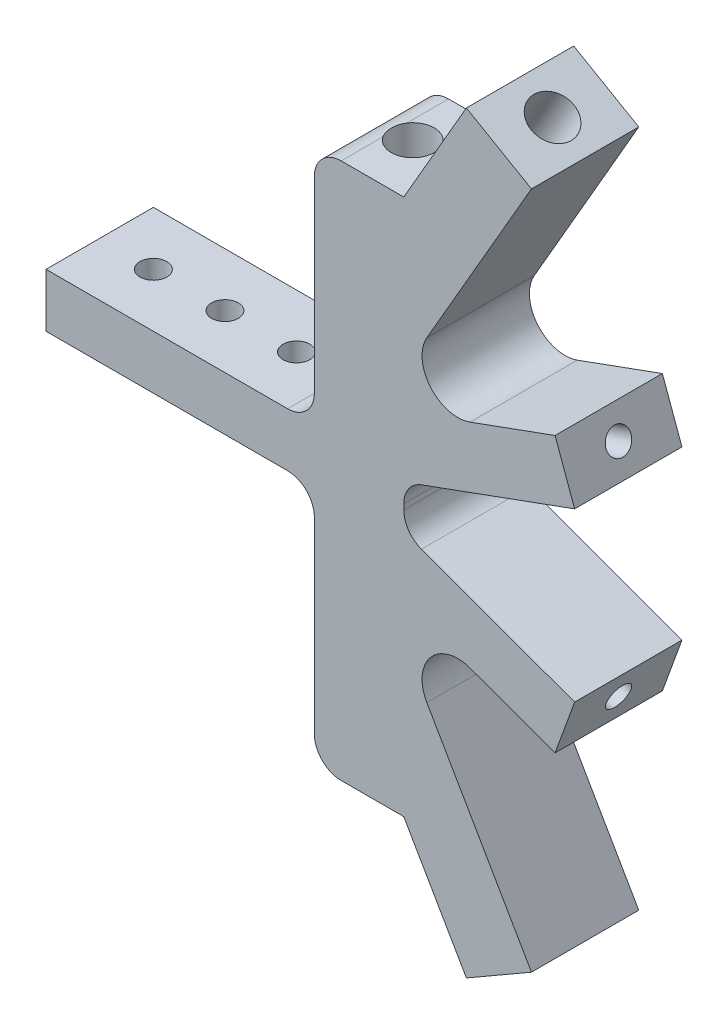
SolidWorks part; units mm, degrees
ref_plane "前基準面" through (0, 0, 0) normal (0, 0, 1) x (1, 0, 0)
ref_plane "上基準面" through (0, 0, 0) normal (0, 1, 0) x (1, 0, 0)
ref_plane "右基準面" through (0, 0, 0) normal (1, 0, 0) x (0, 0, -1)
sketch "草圖1" plane through (0, 0, 0) normal (0, 0, 1) x (1, 0, 0)
  line L0 (0, 23.7611) -> (0, -45.4717) construction
  line L1 (-15.5994, 0) -> (20.5033, 0) construction
  line L2 (-2.5, 15) -> (2.5, 15)
  line L3 (-2.5, 15) -> (-2.5, 1.5)
  line L4 (-2.5, -15) -> (2.5, -15)
  line L5 (2.5, 6.6) -> (2.5, 4.6054)
  line L6 (-2.5, 15) -> (2.5, -15) construction
  line L7 (-2.5, -15) -> (2.5, 15) construction
  line L8 (2.5, 15) -> (6, 21.0622)
  line L9 (6, 21.0622) -> (9.6373, 18.9622)
  line L10 (9.6373, 18.9622) -> (2.5, 6.6)
  line L11 (2.5, -15) -> (6, -21.0622)
  line L12 (6, -21.0622) -> (9.6373, -18.9622)
  line L13 (9.6373, -18.9622) -> (2.5, -6.6)
  line L14 (2.5, 4.6054) -> (10.9572, 7.6836)
  line L15 (10.9572, 7.6836) -> (12.0517, 4.6765)
  line L16 (12.0517, 4.6765) -> (2.5, 1.2)
  line L17 (2.5, -1.2) -> (12.0517, -4.6765)
  line L18 (12.0517, -4.6765) -> (10.9572, -7.6836)
  line L19 (10.9572, -7.6836) -> (2.5, -4.6054)
  line L20 (2.5, 1.2) -> (2.5, -1.2)
  line L21 (-17.5, 1.5) -> (-2.5, 1.5)
  line L22 (-17.5, 1.5) -> (-17.5, -1.5)
  line L23 (-17.5, -1.5) -> (-2.5, -1.5)
  line L25 (-17.5, 1.5) -> (-2.5, -1.5) construction
  line L26 (-17.5, -1.5) -> (-2.5, 1.5) construction
  line L27 (2.5, -4.6054) -> (2.5, -6.6)
  line L28 (-2.5, -1.5) -> (-2.5, -15)
  point P3 (0, 0)
  point P22 (-10, 0)
  dimension "D1" = 5
  dimension "D2" = 30
  dimension "D3" = 60
  dimension "D4" = 60
  dimension "D5" = 7
  dimension "D6" = 7
  dimension "D7" = 40
  dimension "D8" = 40
  dimension "D9" = 9
  dimension "D10" = 9
  dimension "D11" = 4.2
  dimension "D12" = 3.2
  dimension "D13" = 1.2
  dimension "D14" = 1.2
  dimension "D15" = 1.5
  dimension "D16" = 3
  dimension "D17" = 15
  dimension "D18" = 4.2
extrude "填料-伸長1" add sketch "草圖1" along normal blind 6
fillet "圓角4" radius 1.5 6 edges at (-2.5, -1.5, 3) (-2.5, 1.5, 3) (2.5, -4.6054, 3) (2.5, -1.2, 3) (2.5, 1.2, 3) (2.5, 4.6054, 3)
fillet "圓角5" radius 2 2 edges at (2.5, -6.6, 3) (2.5, 6.6, 3)
sketch "草圖7" plane through (10.6202, 18.3947, 0) normal (0.5, 0.866, 0) x (0.866, -0.5, 0)
  line L0 (-1.1349, -6) -> (-1.1349, 0) construction
  line L1 (-1.1349, 0) -> (-5.3349, 0) construction
  circle A0 centre (-3.2349, -3) radius 1.2
  dimension "D1" = 2.4
  dimension "D2" = 2.1
  dimension "D3" = 3
extrude "除料-伸長6" cut sketch "草圖7" against normal blind 10
sketch "草圖8" plane through (10.6202, -18.3947, 0) normal (0.5, -0.866, 0) x (0.866, 0.5, 0)
  line L2 (-1.1349, 6) -> (-1.1349, 0) construction
  line L3 (-5.3349, 0) -> (-1.1349, 0) construction
  circle A0 centre (-3.2349, 3) radius 0.7
  dimension "D3" = 1.4
  dimension "D1" = 3
  dimension "D2" = 2.1
extrude "除料-伸長7" cut sketch "草圖8" against normal blind 10
sketch "草圖9" plane through (12.1449, -4.4204, 0) normal (0.9397, -0.342, 0) x (0, 0, -1)
  line L1 (0, -3.4726) -> (0, -0.2726) construction
  line L2 (-6, -3.4726) -> (0, -3.4726) construction
  circle A0 centre (-3, -1.8726) radius 0.7
  dimension "D3" = 1.4
  dimension "D1" = 1.6
  dimension "D2" = 3
extrude "除料-伸長8" cut sketch "草圖9" against normal blind 10
sketch "草圖10" plane through (12.1449, 4.4204, 0) normal (0.9397, 0.342, 0) x (0, 0, -1)
  line L0 (-6, 3.4726) -> (0, 3.4726) construction
  line L1 (0, 0.2726) -> (0, 3.4726) construction
  circle A0 centre (-3, 1.8726) radius 0.7
  dimension "D3" = 1.4
  dimension "D1" = 1.6
  dimension "D2" = 3
extrude "除料-伸長9" cut sketch "草圖10" against normal blind 10
sketch "草圖11" plane through (0, -15, 0) normal (0, -1, 0) x (1, 0, 0)
  line L0 (2.5, 6) -> (-2.5, 6) construction
  circle A0 centre (0, 3) radius 1.2
  point P2 (0, 6)
  dimension "D1" = 2.4
  dimension "D2" = 3
extrude "除料-伸長10" cut sketch "草圖11" against normal up to next
fillet "圓角6" radius 1.5 2 edges at (-2.5, -15, 3) (-2.5, 15, 3)
sketch "草圖12" plane through (0, -1.5, 0) normal (0, -1, 0) x (1, 0, 0)
  line L0 (-17.5, 6) -> (-17.5, 0) construction
  line L2 (-17.5, 0) -> (-4, 0) construction
  circle A0 centre (-6.5, 3) radius 0.75
  circle A1 centre (-10.5, 3) radius 0.75
  circle A2 centre (-14.5, 3) radius 0.75
  dimension "D5" = 1.5
  dimension "D6" = 1.5
  dimension "D7" = 1.5
  dimension "D1" = 4
  dimension "D2" = 4
  dimension "D3" = 3
  dimension "D4" = 3
extrude "除料-伸長11" cut sketch "草圖12" against normal up to next
